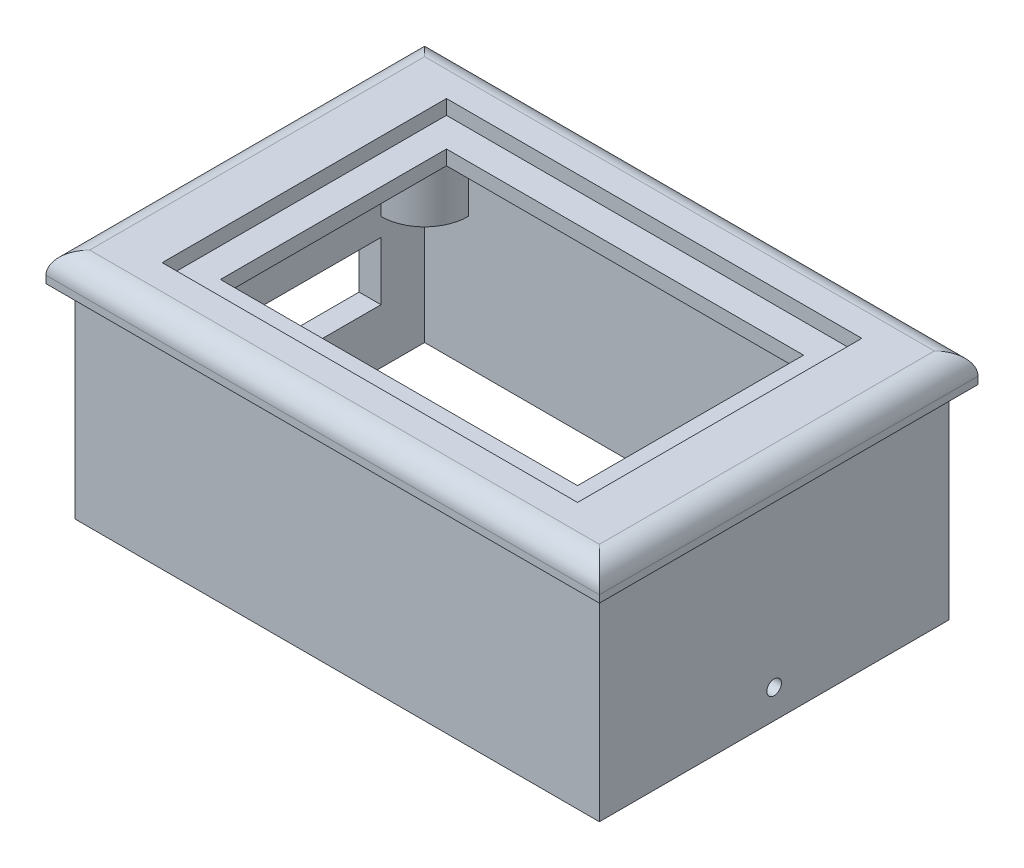
SolidWorks part; units mm, degrees
ref_plane "Front Plane" through (0, 0, 0) normal (0, 0, 1) x (1, 0, 0)
ref_plane "Top Plane" through (0, 0, 0) normal (0, 1, 0) x (1, 0, 0)
ref_plane "Right Plane" through (0, 0, 0) normal (1, 0, 0) x (0, 0, -1)
sketch "Sketch1" plane through (0, 0, 0) normal (0, 1, 0) x (1, 0, 0)
  line L0 (60.325, 41.275) -> (-60.325, 41.275)
  line L1 (57.15, -38.1) -> (-57.15, -38.1) construction
  line L2 (57.15, -38.1) -> (57.15, 38.1) construction
  line L3 (57.15, 38.1) -> (-57.15, 38.1) construction
  line L4 (-57.15, -38.1) -> (-57.15, 38.1) construction
  line L5 (57.15, -38.1) -> (-57.15, 38.1) construction
  line L6 (57.15, 38.1) -> (-57.15, -38.1) construction
  line L7 (-60.325, -41.275) -> (-60.325, 41.275)
  line L8 (60.325, -41.275) -> (-60.325, -41.275)
  line L9 (60.325, -41.275) -> (60.325, 41.275)
  point P0 (0, 0)
  dimension "D1" = 76.2
  dimension "D2" = 114.3
  dimension "D3" = 3.175
extrude "MainBody" add sketch "Sketch1" along normal blind 50.8
sketch "Sketch2" plane through (0, 50.8, 0) normal (0, 1, 0) x (1, 0, 0)
  line L0 (-45.2763, -30.9888) -> (-45.2763, 30.9888)
  line L1 (44.45, -30.1625) -> (-44.45, -30.1625) construction
  line L2 (44.45, -30.1625) -> (44.45, 30.1625) construction
  line L3 (44.45, 30.1625) -> (-44.45, 30.1625) construction
  line L4 (-44.45, -30.1625) -> (-44.45, 30.1625) construction
  line L5 (44.45, -30.1625) -> (-44.45, 30.1625) construction
  line L6 (44.45, 30.1625) -> (-44.45, -30.1625) construction
  line L7 (45.2763, 30.9888) -> (-45.2763, 30.9888)
  line L8 (45.2763, -30.9888) -> (45.2763, 30.9888)
  line L9 (45.2763, -30.9888) -> (-45.2763, -30.9888)
  point P0 (0, 0)
  dimension "D1" = 60.325
  dimension "D2" = 88.9
  dimension "D3" = 0.8263
extrude "SolarPanelRecess" cut sketch "Sketch2" against normal blind 3.175
sketch "Sketch3" plane through (0, 47.625, 0) normal (0, 1, 0) x (1, 0, 0)
  line L16 (38.9263, 24.6388) -> (-38.9263, 24.6388)
  line L17 (-38.9263, 24.6388) -> (-38.9263, -24.6388)
  line L18 (-38.9263, -24.6388) -> (38.9263, -24.6388)
  line L19 (38.9263, -24.6388) -> (38.9263, 24.6388)
  line L20 (38.9263, 24.6388) -> (-38.9263, 24.6388)
  line L21 (-38.9263, 24.6388) -> (-38.9263, -24.6388)
  line L22 (-38.9263, -24.6388) -> (38.9263, -24.6388)
  line L23 (38.9263, -24.6388) -> (38.9263, 24.6388)
  dimension "D1" = 6.35
extrude "SolarPanelWiringRecess" cut sketch "Sketch3" against normal through all
sketch "Sketch4" plane through (0, 0, 0) normal (0, -1, 0) x (1, 0, 0)
  line L0 (-63.5, -44.45) -> (63.5, -44.45)
  line L1 (52.3875, -33.3375) -> (-52.3875, -33.3375)
  line L2 (52.3875, -33.3375) -> (52.3875, 33.3375)
  line L3 (52.3875, 33.3375) -> (-52.3875, 33.3375)
  line L4 (-52.3875, -33.3375) -> (-52.3875, 33.3375)
  line L5 (52.3875, -33.3375) -> (-52.3875, 33.3375) construction
  line L6 (52.3875, 33.3375) -> (-52.3875, -33.3375) construction
  line L7 (-57.15, 38.1) -> (57.15, 38.1)
  line L8 (-57.15, 38.1) -> (-57.15, -38.1)
  line L9 (-57.15, -38.1) -> (57.15, -38.1)
  line L10 (57.15, 38.1) -> (57.15, -38.1)
  line L11 (-57.15, 38.1) -> (57.15, -38.1) construction
  line L12 (-57.15, -38.1) -> (57.15, 38.1) construction
  line L13 (63.5, 44.45) -> (63.5, -44.45)
  line L14 (-63.5, 44.45) -> (63.5, 44.45)
  line L15 (-63.5, 44.45) -> (-63.5, -44.45)
  point P0 (0, 0)
  point P6 (0, 0)
  line M13 (60.325, -41.275) -> (60.325, 41.275)
  line M14 (60.325, 41.275) -> (-60.325, 41.275)
  line M15 (-60.325, 41.275) -> (-60.325, -41.275)
  line M16 (-60.325, -41.275) -> (60.325, -41.275)
  dimension "D1" = 66.675
  dimension "D2" = 104.775
  dimension "D3" = 114.3
  dimension "D4" = 76.2
  dimension "D5" = 6.35
extrude "InsideEnclosureRecess_OutsideFlange" cut sketch "Sketch4" against normal offset from surface (44.45 mm away) 3.175 contours L14 L15 L0 L13 M13 M16 M15 M14 | L7 L10 L9 L8 M16 M13 M14 M15 | L4 L1 L2 L3 region at (-61.9498, 0, 0) region at (0, 0, 0) region at (0, 0, -39.8131) up to face at (0, 47.625, 0)
fillet "Fillet1" radius 4.7625 4 edges at (60.325, 50.8, 0) (0, 50.8, 41.275) (-60.325, 50.8, 0) (0, 50.8, -41.275)
sketch "Sketch6" plane through (-57.15, 0, 0) normal (-1, 0, 0) x (0, 0, 1)
  line L1 (-14.2875, 25.4) -> (14.2875, 25.4) construction
  line L2 (-14.2875, 24.6063) -> (14.2875, 24.6063)
  line L3 (14.2875, 24.6063) -> (26.9875, 24.6063)
  line L4 (26.9875, 24.6063) -> (26.9875, 11.9063)
  line L5 (26.9875, 11.9063) -> (-23.8125, 11.9062)
  line L6 (-23.8125, 11.9062) -> (-23.8125, 24.6063)
  line L7 (-23.8125, 24.6063) -> (-14.2875, 24.6063)
  dimension "D2" = 6.35
  dimension "D3" = 9.525
  dimension "D4" = 12.7
  dimension "D1" = 0.7937
extrude "CableAccess" cut sketch "Sketch6" against normal up to next
sketch "Sketch9" plane through (57.15, 0, 0) normal (1, 0, 0) x (0, 0, -1)
  line L0 (0, 0) -> (0, 6.35) construction
  line L1 (-38.1, 0) -> (38.1, 0) construction
  circle A0 centre (0, 6.35) radius 1.5875
  dimension "D1" = 3.175
  dimension "D2" = 6.35
extrude "TopEdgeHoles" cut sketch "Sketch9" against normal through all
sketch "Sketch10" plane through (0, 44.45, 0) normal (0, -1, 0) x (1, 0, 0)
  line L0 (-52.3875, 33.3375) -> (-52.3875, -33.3375) construction
  line L1 (50.0062, 31.75) -> (-50.0063, 31.75) construction
  line L2 (50.0062, 31.75) -> (50.0062, -31.75) construction
  line L3 (50.0062, -31.75) -> (-50.0063, -31.75) construction
  line L4 (-50.0063, 31.75) -> (-50.0063, -31.75) construction
  line L5 (50.0062, 31.75) -> (-50.0063, -31.75) construction
  line L6 (50.0062, -31.75) -> (-50.0063, 31.75) construction
  line L7 (-52.3875, 33.3375) -> (52.3875, 33.3375) construction
  line L8 (-52.3875, 33.3375) -> (-52.3875, 23.8125)
  line L9 (-52.3875, 33.3375) -> (-42.8625, 33.3375)
  line L10 (-42.8625, 33.3375) -> (52.3875, 33.3375) construction
  line L11 (-52.3875, 23.8125) -> (-52.3875, -33.3375) construction
  line L12 (-52.3875, -33.3375) -> (52.3875, -33.3375) construction
  arc A0 (-52.3875, 23.8125) -> (-42.8625, 33.3375) centre (-52.3875, 33.3375) ccw
  arc A1 (-42.8625, 33.3375) -> (-52.3875, 23.8125) centre (-52.3875, 33.3375) ccw construction
  circle A2 centre (-52.3875, -33.3375) radius 9.525
  circle A3 centre (52.3875, -33.3375) radius 9.525
  circle A4 centre (52.3875, 33.3375) radius 9.525
  point P0 (0, 0)
  line M12 (52.3875, 33.3375) -> (-52.3875, 33.3375)
  line M13 (-52.3875, 33.3375) -> (-52.3875, -33.3375)
  line M14 (-52.3875, -33.3375) -> (52.3875, -33.3375)
  line M15 (52.3875, -33.3375) -> (52.3875, 33.3375)
  dimension "D3" = 19.05
  dimension "D1" = 63.5
  dimension "D2" = 100.0125
extrude "CornerStandoffs" add sketch "Sketch10" along normal blind 15.875 contours A0 M13 M12 | A4 M12 M15 | A2 M14 M13 | A3 M15 M14 region at (-48.345, 44.45, 29.295) region at (-48.345, 44.45, -29.295) region at (48.345, 44.45, 29.295) region at (48.345, 44.45, -29.295)
sketch "Sketch11" plane through (0, 28.575, 0) normal (0, -1, 0) x (1, 0, 0)
  line L0 (50.0062, 31.75) -> (-50.0063, 31.75) construction
  line L1 (-50.0063, 31.75) -> (-50.0063, -31.75) construction
  line L2 (50.0062, -31.75) -> (-50.0063, -31.75) construction
  line L3 (50.0062, 31.75) -> (50.0062, -31.75) construction
  line L4 (50.0062, 31.75) -> (-50.0063, 31.75) construction
  line L5 (-50.0063, 31.75) -> (-50.0063, -31.75) construction
  line L6 (50.0062, -31.75) -> (-50.0063, -31.75) construction
  line L7 (50.0062, 31.75) -> (50.0062, -31.75) construction
  line L8 (46.8312, 28.575) -> (46.8312, -28.575) construction
  line L9 (46.8312, -28.575) -> (-46.8313, -28.575) construction
  line L10 (-46.8313, 28.575) -> (-46.8313, -28.575) construction
  line L11 (46.8312, 28.575) -> (-46.8313, 28.575) construction
  circle A0 centre (46.8312, -28.575) radius 1.143
  circle A1 centre (-46.8313, -28.575) radius 1.143
  circle A2 centre (-46.8313, 28.575) radius 1.143
  circle A3 centre (46.8312, 28.575) radius 1.143
  dimension "D2" = 2.286
  dimension "D1" = 3.175
extrude "ScrewStandoffHoles" cut sketch "Sketch11" against normal blind 6.35
sketch "Sketch12" plane through (0, 0, 0) normal (0, -1, 0) x (1, 0, 0)
  line L4 (53.975, -34.925) -> (53.975, 34.925)
  line L5 (53.975, 34.925) -> (-53.975, 34.925)
  line L6 (-53.975, 34.925) -> (-53.975, -34.925)
  line L7 (-53.975, -34.925) -> (53.975, -34.925)
  line L8 (55.5625, -36.5125) -> (55.5625, 36.5125)
  line L9 (55.5625, 36.5125) -> (-55.5625, 36.5125)
  line L10 (-55.5625, 36.5125) -> (-55.5625, -36.5125)
  line L11 (-55.5625, -36.5125) -> (55.5625, -36.5125)
  line L12 (55.5625, -36.5125) -> (55.5625, 36.5125)
  line L13 (55.5625, 36.5125) -> (-55.5625, 36.5125)
  line L14 (-55.5625, 36.5125) -> (-55.5625, -36.5125)
  line L15 (-55.5625, -36.5125) -> (55.5625, -36.5125)
  dimension "D1" = 1.5875
  dimension "D2" = 1.5875
extrude "Cut-Extrude5" cut sketch "Sketch12" against normal blind 3.175
